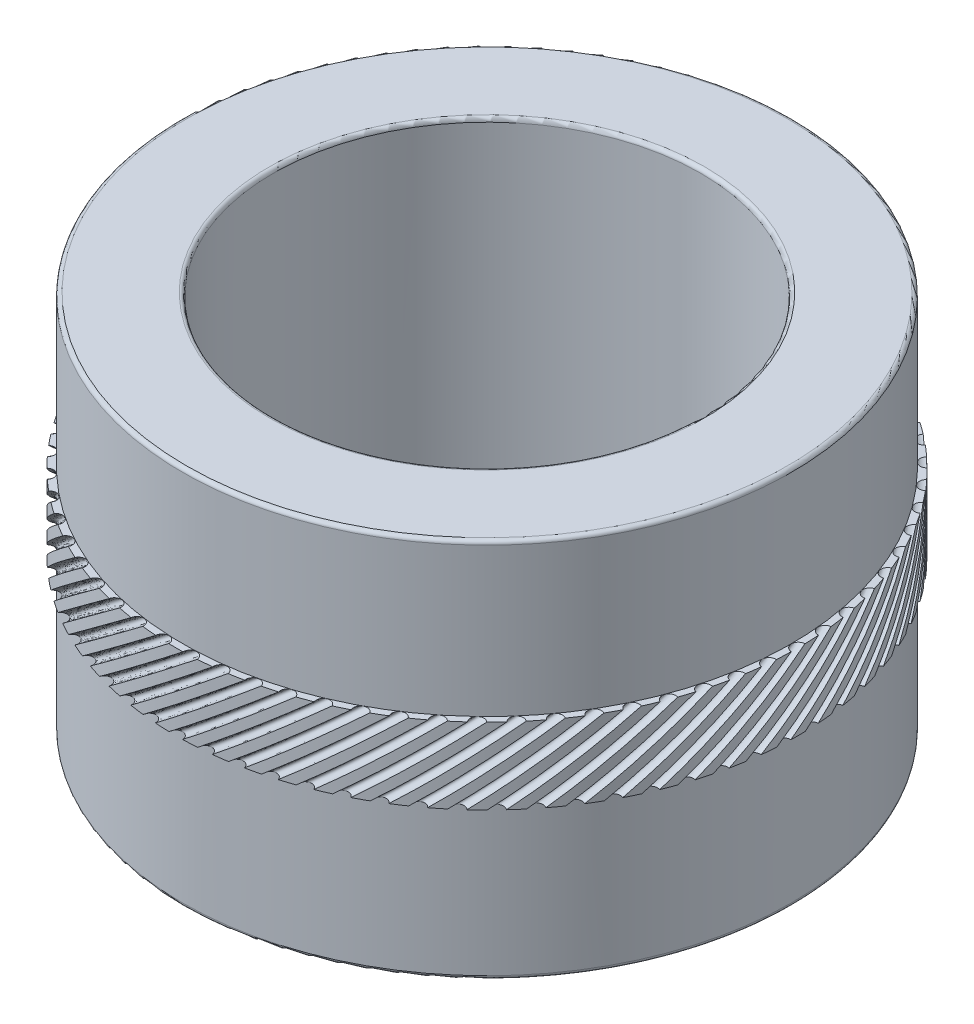
SolidWorks part; units mm, degrees
ref_plane "Front" through (0, 0, 0) normal (0, 0, 1) x (1, 0, 0)
ref_plane "Top" through (0, 0, 0) normal (0, 1, 0) x (1, 0, 0)
ref_plane "Right" through (0, 0, 0) normal (1, 0, 0) x (0, 0, -1)
sketch "Layout " plane through (0, 0, 0) normal (0, 0, 1) x (1, 0, 0)
  line L0 (0, 0) -> (0, 6.35) construction
  point P3 (-5.08, 6.35)
  point P4 (-3.5687, 6.35)
  point P5 (-5.1943, 6.35)
sketch "Sketch2" plane through (0, 0, 0) normal (0, 0, 1) x (1, 0, 0)
  line L0 (0, 0) -> (0, 6.35) construction
  line L1 (0, 0) -> (0, 6.35) construction
  line L2 (-3.5687, 6.35) -> (-5.08, 6.35)
  line L3 (-5.08, 6.35) -> (-5.08, 3.81)
  line L4 (-5.08, 3.81) -> (-5.1943, 3.81)
  line L5 (0, 3.175) -> (-5.1943, 3.175) construction
  line L6 (-5.1943, 3.81) -> (-5.1943, 2.54)
  line L7 (-3.5687, 0) -> (-5.08, 0)
  line L8 (-5.08, 0) -> (-5.08, 2.54)
  line L9 (-5.08, 2.54) -> (-5.1943, 2.54)
  line L10 (-3.5687, 6.35) -> (-3.5687, 0)
  dimension "D1" = 1.27
revolve "Revolve1" add sketch "Sketch2" angle 360 about L1
sketch "Sketch3" plane through (0, 3.81, 0) normal (0, 1, 0) x (1, 0, 0)
  circle A0 centre (0, 0) radius 5.1943 construction
  circle A1 centre (0, 0) radius 5.1943
curve "Helix/Spiral2" pitch 25.4 height 1.27 radius 5.1943 centre (0, 3.81, 0) axis (0, -1, 0) start towards (1, 0, 0)
sketch "Sketch4" plane through (0, 3.81, 0) normal (0, 1, 0) x (1, 0, 0)
  line L0 (0, 0) -> (5.1943, 0.1133) construction
  line L1 (0, 0) -> (5.1943, -0.1133) construction
  circle A0 centre (5.1943, 0) radius 0.1133
  circle A1 centre (0, 0) radius 5.1943 construction
  circle A3 centre (0, 0) radius 5.08 construction
  circle A4 centre (0, 0) radius 5.08 construction
  spline S0 degree 3 poles (5.1943, 0) (5.1943, -0.1813) (5.1753, -0.544) (5.0901, -1.0819) (4.9961, -1.4327) (4.9401, -1.6051) knots 0 0 0 0 0.333333 0.666667 1 1 1 1 construction
  dimension "D1" = 2.5
sweep "Cut-Sweep1" cut profiles "Sketch4" path "Helix/Spiral2" align with end faces yes
pattern_circular "CirPattern1" count 70 over 360 about axis through (0, 0, 0) along (0, -1, 0) of "Cut-Sweep1"
fillet "Fillet1" radius 0.0635 4 edges at (0, 0, -5.08) (0, 0, -3.5687) (0, 6.35, -3.5687) (0, 6.35, -5.08)
equation "\"D1@Sketch2\"=\"Length@Layout \"*.2"
equation "\"D3@Helix/Spiral2\"=\"D1@Sketch2\""
